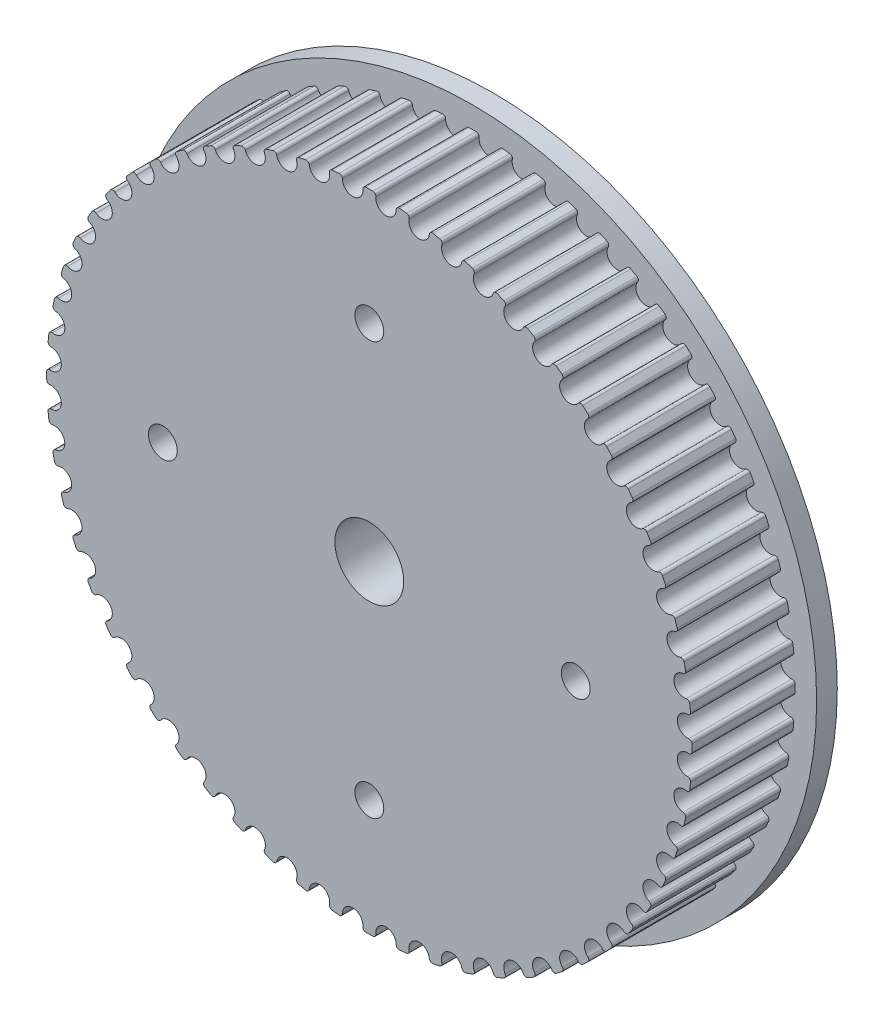
SolidWorks part; units mm, degrees
material "PE High Density"
ref_plane "Front Plane" through (0, 0, 0) normal (0, 0, 1) x (1, 0, 0)
ref_plane "Top Plane" through (0, 0, 0) normal (0, 1, 0) x (1, 0, 0)
ref_plane "Right Plane" through (0, 0, 0) normal (1, 0, 0) x (0, 0, -1)
sketch "Sketch2" plane through (0, 0, 0) normal (0, 0, 1) x (1, 0, 0)
  circle A0 centre (0, 0) radius 47.7465
  dimension "D1" = 95.493
extrude "PD" add sketch "Sketch2" along normal mid plane 15
sketch "Sketch3" plane through (0, 0, 7.5) normal (0, 0, 1) x (1, 0, 0)
  line L0 (0, 0) -> (0, 46.8765) construction
  line L1 (0, 0) -> (2.4235, 46.243) construction
  line L2 (0, 46.8765) -> (0.5143, 46.8765)
  line L3 (0, 46.8765) -> (0, 47.7465)
  line L4 (4.8999, 46.6197) -> (4.9909, 47.4849)
  line L5 (4.8999, 46.6197) -> (4.3884, 46.6734)
  line L6 (2.4235, 46.243) -> (2.4989, 47.681) construction
  arc A0 (0.5143, 46.8765) -> (0.9419, 46.4009) centre (0.5143, 46.4465) cw
  arc A1 (0.9419, 46.4009) -> (3.9135, 46.2452) centre (2.4235, 46.243) ccw
  circle A2 centre (0, 0) radius 47.7465 construction
  arc A3 (0, 47.7465) -> (4.9909, 47.4849) centre (0, 0) cw
  arc A4 (4.3884, 46.6734) -> (3.9135, 46.2452) centre (4.3435, 46.2458) ccw
  point P8 (2.3455, 44.7551)
  dimension "D1" = 0.43
  dimension "D2" = 1.49
  dimension "D3" = 0.87
  dimension "D4" = 3
  dimension "D5" = 2.93
extrude "Teeth" cut sketch "Sketch3" against normal up to surface (15 mm away) up to face at (47.7465, 0, -7.5)
pattern_circular "CirPattern1" count 60 over 360 about axis through (0, 0, 7.5) along (0, 0, 1) of "Teeth"
sketch "Sketch7" [suppressed] plane through (0, 0, -7.5) normal (0, 0, -1) x (-1, 0, 0)
  circle A0 centre (0, 6) radius 1.25
  circle A2 centre (6, 0) radius 1.25
  circle A3 centre (0, -6) radius 1.25
  circle A4 centre (-6, 0) radius 1.25
  point P12 (0, 0)
  dimension "D1" = 6
  dimension "D2" = 4
extrude "Cut-Extrude3" [suppressed] cut sketch "Sketch7" against normal blind 21
sketch "Sketch8" [suppressed] plane through (0, 0, -7.5) normal (0, 0, -1) x (-1, 0, 0)
  circle A0 centre (0, 0) radius 2.5
extrude "Cut-Extrude4" [suppressed] cut sketch "Sketch8" against normal blind 25
sketch "Sketch10" plane through (0, 0, -7.5) normal (0, 0, -1) x (-1, 0, 0)
  circle A0 centre (0, 0) radius 50
  dimension "D1" = 100
extrude "Boss-Extrude1" add sketch "Sketch10" along normal blind 3
sketch "Sketch12" [suppressed] plane through (0, 0, -7.5) normal (0, 0, -1) x (-1, 0, 0)
  circle A0 centre (0, 0) radius 13.5
  circle A1 centre (0, 6) radius 1.25 construction
  circle A2 centre (6, 0) radius 1.25 construction
  circle A3 centre (0, -6) radius 1.25 construction
  circle A4 centre (0, 0) radius 2.5 construction
  circle A5 centre (-6, 0) radius 1.25 construction
  circle A6 centre (0, 6) radius 1.25
  circle A7 centre (6, 0) radius 1.25
  circle A8 centre (0, -6) radius 1.25
  circle A9 centre (0, 0) radius 2.5
  circle A10 centre (-6, 0) radius 1.25
  dimension "D1" = 27
extrude "Boss-Extrude2" [suppressed] add sketch "Sketch12" along normal blind 3
sketch "Sketch13" [suppressed] plane through (0, 0, 7.5) normal (0, 0, 1) x (1, 0, 0)
  line L16 (0.3165, 11.8624) -> (-0.3165, 11.8624)
  line L17 (-4.2471, 11.0805) -> (-4.832, 10.8383)
  line L18 (-8.1642, 8.6118) -> (-8.6118, 8.1642)
  line L19 (-10.8383, 4.832) -> (-11.0805, 4.2471)
  line L20 (-11.8624, 0.3165) -> (-11.8624, -0.3165)
  line L21 (-11.0805, -4.2471) -> (-10.8383, -4.832)
  line L22 (-8.6118, -8.1642) -> (-8.1642, -8.6118)
  line L23 (-4.832, -10.8383) -> (-4.2471, -11.0805)
  line L24 (-0.3165, -11.8624) -> (0.3165, -11.8624)
  line L25 (4.2471, -11.0805) -> (4.832, -10.8383)
  line L26 (8.1642, -8.6118) -> (8.6118, -8.1642)
  line L27 (10.8383, -4.832) -> (11.0805, -4.2471)
  line L28 (11.8624, -0.3165) -> (11.8624, 0.3165)
  line L29 (11.0805, 4.2471) -> (10.8383, 4.832)
  line L30 (8.6118, 8.1642) -> (8.1642, 8.6118)
  line L31 (4.832, 10.8383) -> (4.2471, 11.0805)
  line L32 (0.3165, 11.8624) -> (-0.3165, 11.8624)
  line L33 (-4.2471, 11.0805) -> (-4.832, 10.8383)
  line L34 (-8.1642, 8.6118) -> (-8.6118, 8.1642)
  line L35 (-10.8383, 4.832) -> (-11.0805, 4.2471)
  line L36 (-11.8624, 0.3165) -> (-11.8624, -0.3165)
  line L37 (-11.0805, -4.2471) -> (-10.8383, -4.832)
  line L38 (-8.6118, -8.1642) -> (-8.1642, -8.6118)
  line L39 (-4.832, -10.8383) -> (-4.2471, -11.0805)
  line L40 (-0.3165, -11.8624) -> (0.3165, -11.8624)
  line L41 (4.2471, -11.0805) -> (4.832, -10.8383)
  line L42 (8.1642, -8.6118) -> (8.6118, -8.1642)
  line L43 (10.8383, -4.832) -> (11.0805, -4.2471)
  line L44 (11.8624, -0.3165) -> (11.8624, 0.3165)
  line L45 (11.0805, 4.2471) -> (10.8383, 4.832)
  line L46 (8.6118, 8.1642) -> (8.1642, 8.6118)
  line L47 (4.832, 10.8383) -> (4.2471, 11.0805)
  arc A48 (-0.3165, 11.8624) -> (-0.739, 11.3524) centre (-0.3165, 11.4324) ccw
  arc A49 (-3.6616, 10.7711) -> (-0.739, 11.3524) centre (-2.203, 11.0754) ccw
  arc A50 (-3.6616, 10.7711) -> (-4.2471, 11.0805) centre (-4.0826, 10.6833) ccw
  arc A51 (-4.832, 10.8383) -> (-5.0272, 10.2055) centre (-4.6674, 10.441) ccw
  arc A52 (-7.5048, 8.55) -> (-5.0272, 10.2055) centre (-6.2737, 9.3893) ccw
  arc A53 (-7.5048, 8.55) -> (-8.1642, 8.6118) centre (-7.8601, 8.3077) ccw
  arc A54 (-8.6118, 8.1642) -> (-8.55, 7.5048) centre (-8.3077, 7.8601) ccw
  arc A55 (-10.2055, 5.0272) -> (-8.55, 7.5048) centre (-9.3893, 6.2737) ccw
  arc A56 (-10.2055, 5.0272) -> (-10.8383, 4.832) centre (-10.441, 4.6674) ccw
  arc A57 (-11.0805, 4.2471) -> (-10.7711, 3.6616) centre (-10.6833, 4.0826) ccw
  arc A58 (-11.3524, 0.739) -> (-10.7711, 3.6616) centre (-11.0754, 2.203) ccw
  arc A59 (-11.3524, 0.739) -> (-11.8624, 0.3165) centre (-11.4324, 0.3165) ccw
  arc A60 (-11.8624, -0.3165) -> (-11.3524, -0.739) centre (-11.4324, -0.3165) ccw
  arc A61 (-10.7711, -3.6616) -> (-11.3524, -0.739) centre (-11.0754, -2.203) ccw
  arc A62 (-10.7711, -3.6616) -> (-11.0805, -4.2471) centre (-10.6833, -4.0826) ccw
  arc A63 (-10.8383, -4.832) -> (-10.2055, -5.0272) centre (-10.441, -4.6674) ccw
  arc A64 (-8.55, -7.5048) -> (-10.2055, -5.0272) centre (-9.3893, -6.2737) ccw
  arc A65 (-8.55, -7.5048) -> (-8.6118, -8.1642) centre (-8.3077, -7.8601) ccw
  arc A66 (-8.1642, -8.6118) -> (-7.5048, -8.55) centre (-7.8601, -8.3077) ccw
  arc A67 (-5.0272, -10.2055) -> (-7.5048, -8.55) centre (-6.2737, -9.3893) ccw
  arc A68 (-5.0272, -10.2055) -> (-4.832, -10.8383) centre (-4.6674, -10.441) ccw
  arc A69 (-4.2471, -11.0805) -> (-3.6616, -10.7711) centre (-4.0826, -10.6833) ccw
  arc A70 (-0.739, -11.3524) -> (-3.6616, -10.7711) centre (-2.203, -11.0754) ccw
  arc A71 (-0.739, -11.3524) -> (-0.3165, -11.8624) centre (-0.3165, -11.4324) ccw
  arc A72 (0.3165, -11.8624) -> (0.739, -11.3524) centre (0.3165, -11.4324) ccw
  arc A73 (3.6616, -10.7711) -> (0.739, -11.3524) centre (2.203, -11.0754) ccw
  arc A74 (3.6616, -10.7711) -> (4.2471, -11.0805) centre (4.0826, -10.6833) ccw
  arc A75 (4.832, -10.8383) -> (5.0272, -10.2055) centre (4.6674, -10.441) ccw
  arc A76 (7.5048, -8.55) -> (5.0272, -10.2055) centre (6.2737, -9.3893) ccw
  arc A77 (7.5048, -8.55) -> (8.1642, -8.6118) centre (7.8601, -8.3077) ccw
  arc A78 (8.6118, -8.1642) -> (8.55, -7.5048) centre (8.3077, -7.8601) ccw
  arc A79 (10.2055, -5.0272) -> (8.55, -7.5048) centre (9.3893, -6.2737) ccw
  arc A80 (10.2055, -5.0272) -> (10.8383, -4.832) centre (10.441, -4.6674) ccw
  arc A81 (11.0805, -4.2471) -> (10.7711, -3.6616) centre (10.6833, -4.0826) ccw
  arc A82 (11.3524, -0.739) -> (10.7711, -3.6616) centre (11.0754, -2.203) ccw
  arc A83 (11.3524, -0.739) -> (11.8624, -0.3165) centre (11.4324, -0.3165) ccw
  arc A84 (11.8624, 0.3165) -> (11.3524, 0.739) centre (11.4324, 0.3165) ccw
  arc A85 (10.7711, 3.6616) -> (11.3524, 0.739) centre (11.0754, 2.203) ccw
  arc A86 (10.7711, 3.6616) -> (11.0805, 4.2471) centre (10.6833, 4.0826) ccw
  arc A87 (10.8383, 4.832) -> (10.2055, 5.0272) centre (10.441, 4.6674) ccw
  arc A88 (8.55, 7.5048) -> (10.2055, 5.0272) centre (9.3893, 6.2737) ccw
  arc A89 (8.55, 7.5048) -> (8.6118, 8.1642) centre (8.3077, 7.8601) ccw
  arc A90 (8.1642, 8.6118) -> (7.5048, 8.55) centre (7.8601, 8.3077) ccw
  arc A91 (5.0272, 10.2055) -> (7.5048, 8.55) centre (6.2737, 9.3893) ccw
  arc A92 (5.0272, 10.2055) -> (4.832, 10.8383) centre (4.6674, 10.441) ccw
  arc A93 (4.2471, 11.0805) -> (3.6616, 10.7711) centre (4.0826, 10.6833) ccw
  arc A94 (0.739, 11.3524) -> (3.6616, 10.7711) centre (2.203, 11.0754) ccw
  arc A95 (0.739, 11.3524) -> (0.3165, 11.8624) centre (0.3165, 11.4324) ccw
  arc A96 (-0.3165, 11.8624) -> (-0.739, 11.3524) centre (-0.3165, 11.4324) ccw
  arc A97 (-3.6616, 10.7711) -> (-0.739, 11.3524) centre (-2.203, 11.0754) ccw
  arc A98 (-3.6616, 10.7711) -> (-4.2471, 11.0805) centre (-4.0826, 10.6833) ccw
  arc A99 (-4.832, 10.8383) -> (-5.0272, 10.2055) centre (-4.6674, 10.441) ccw
  arc A100 (-7.5048, 8.55) -> (-5.0272, 10.2055) centre (-6.2737, 9.3893) ccw
  arc A101 (-7.5048, 8.55) -> (-8.1642, 8.6118) centre (-7.8601, 8.3077) ccw
  arc A102 (-8.6118, 8.1642) -> (-8.55, 7.5048) centre (-8.3077, 7.8601) ccw
  arc A103 (-10.2055, 5.0272) -> (-8.55, 7.5048) centre (-9.3893, 6.2737) ccw
  arc A104 (-10.2055, 5.0272) -> (-10.8383, 4.832) centre (-10.441, 4.6674) ccw
  arc A105 (-11.0805, 4.2471) -> (-10.7711, 3.6616) centre (-10.6833, 4.0826) ccw
  arc A106 (-11.3524, 0.739) -> (-10.7711, 3.6616) centre (-11.0754, 2.203) ccw
  arc A107 (-11.3524, 0.739) -> (-11.8624, 0.3165) centre (-11.4324, 0.3165) ccw
  arc A108 (-11.8624, -0.3165) -> (-11.3524, -0.739) centre (-11.4324, -0.3165) ccw
  arc A109 (-10.7711, -3.6616) -> (-11.3524, -0.739) centre (-11.0754, -2.203) ccw
  arc A110 (-10.7711, -3.6616) -> (-11.0805, -4.2471) centre (-10.6833, -4.0826) ccw
  arc A111 (-10.8383, -4.832) -> (-10.2055, -5.0272) centre (-10.441, -4.6674) ccw
  arc A112 (-8.55, -7.5048) -> (-10.2055, -5.0272) centre (-9.3893, -6.2737) ccw
  arc A113 (-8.55, -7.5048) -> (-8.6118, -8.1642) centre (-8.3077, -7.8601) ccw
  arc A114 (-8.1642, -8.6118) -> (-7.5048, -8.55) centre (-7.8601, -8.3077) ccw
  arc A115 (-5.0272, -10.2055) -> (-7.5048, -8.55) centre (-6.2737, -9.3893) ccw
  arc A116 (-5.0272, -10.2055) -> (-4.832, -10.8383) centre (-4.6674, -10.441) ccw
  arc A117 (-4.2471, -11.0805) -> (-3.6616, -10.7711) centre (-4.0826, -10.6833) ccw
  arc A118 (-0.739, -11.3524) -> (-3.6616, -10.7711) centre (-2.203, -11.0754) ccw
  arc A119 (-0.739, -11.3524) -> (-0.3165, -11.8624) centre (-0.3165, -11.4324) ccw
  arc A120 (0.3165, -11.8624) -> (0.739, -11.3524) centre (0.3165, -11.4324) ccw
  arc A121 (3.6616, -10.7711) -> (0.739, -11.3524) centre (2.203, -11.0754) ccw
  arc A122 (3.6616, -10.7711) -> (4.2471, -11.0805) centre (4.0826, -10.6833) ccw
  arc A123 (4.832, -10.8383) -> (5.0272, -10.2055) centre (4.6674, -10.441) ccw
  arc A124 (7.5048, -8.55) -> (5.0272, -10.2055) centre (6.2737, -9.3893) ccw
  arc A125 (7.5048, -8.55) -> (8.1642, -8.6118) centre (7.8601, -8.3077) ccw
  arc A126 (8.6118, -8.1642) -> (8.55, -7.5048) centre (8.3077, -7.8601) ccw
  arc A127 (10.2055, -5.0272) -> (8.55, -7.5048) centre (9.3893, -6.2737) ccw
  arc A128 (10.2055, -5.0272) -> (10.8383, -4.832) centre (10.441, -4.6674) ccw
  arc A129 (11.0805, -4.2471) -> (10.7711, -3.6616) centre (10.6833, -4.0826) ccw
  arc A130 (11.3524, -0.739) -> (10.7711, -3.6616) centre (11.0754, -2.203) ccw
  arc A131 (11.3524, -0.739) -> (11.8624, -0.3165) centre (11.4324, -0.3165) ccw
  arc A132 (11.8624, 0.3165) -> (11.3524, 0.739) centre (11.4324, 0.3165) ccw
  arc A133 (10.7711, 3.6616) -> (11.3524, 0.739) centre (11.0754, 2.203) ccw
  arc A134 (10.7711, 3.6616) -> (11.0805, 4.2471) centre (10.6833, 4.0826) ccw
  arc A135 (10.8383, 4.832) -> (10.2055, 5.0272) centre (10.441, 4.6674) ccw
  arc A136 (8.55, 7.5048) -> (10.2055, 5.0272) centre (9.3893, 6.2737) ccw
  arc A137 (8.55, 7.5048) -> (8.6118, 8.1642) centre (8.3077, 7.8601) ccw
  arc A138 (8.1642, 8.6118) -> (7.5048, 8.55) centre (7.8601, 8.3077) ccw
  arc A139 (5.0272, 10.2055) -> (7.5048, 8.55) centre (6.2737, 9.3893) ccw
  arc A140 (5.0272, 10.2055) -> (4.832, 10.8383) centre (4.6674, 10.441) ccw
  arc A141 (4.2471, 11.0805) -> (3.6616, 10.7711) centre (4.0826, 10.6833) ccw
  arc A142 (0.739, 11.3524) -> (3.6616, 10.7711) centre (2.203, 11.0754) ccw
  arc A143 (0.739, 11.3524) -> (0.3165, 11.8624) centre (0.3165, 11.4324) ccw
  dimension "D1" = 0
sketch "Sketch14" plane through (0, 0, -10.5) normal (0, 0, -1) x (-1, 0, 0)
  line L0 (0.3165, 11.8624) -> (-0.3165, 11.8624)
  line L1 (-4.2471, 11.0805) -> (-4.832, 10.8383)
  line L2 (-8.1642, 8.6118) -> (-8.6118, 8.1642)
  line L3 (-10.8383, 4.832) -> (-11.0805, 4.2471)
  line L4 (-11.8624, 0.3165) -> (-11.8624, -0.3165)
  line L5 (-11.0805, -4.2471) -> (-10.8383, -4.832)
  line L6 (-8.6118, -8.1642) -> (-8.1642, -8.6118)
  line L7 (-4.832, -10.8383) -> (-4.2471, -11.0805)
  line L8 (-0.3165, -11.8624) -> (0.3165, -11.8624)
  line L9 (4.2471, -11.0805) -> (4.832, -10.8383)
  line L10 (8.1642, -8.6118) -> (8.6118, -8.1642)
  line L11 (10.8383, -4.832) -> (11.0805, -4.2471)
  line L12 (11.8624, -0.3165) -> (11.8624, 0.3165)
  line L13 (11.0805, 4.2471) -> (10.8383, 4.832)
  line L14 (8.6118, 8.1642) -> (8.1642, 8.6118)
  line L15 (4.832, 10.8383) -> (4.2471, 11.0805)
  line L16 (-4.5395, 10.9594) -> (4.5395, -10.9594) construction
  arc A0 (-0.3165, 11.8624) -> (-0.739, 11.3524) centre (-0.3165, 11.4324) ccw
  arc A1 (-3.6616, 10.7711) -> (-0.739, 11.3524) centre (-2.203, 11.0754) ccw
  arc A2 (-3.6616, 10.7711) -> (-4.2471, 11.0805) centre (-4.0826, 10.6833) ccw
  arc A3 (-4.832, 10.8383) -> (-5.0272, 10.2055) centre (-4.6674, 10.441) ccw
  arc A4 (-7.5048, 8.55) -> (-5.0272, 10.2055) centre (-6.2737, 9.3893) ccw
  arc A5 (-7.5048, 8.55) -> (-8.1642, 8.6118) centre (-7.8601, 8.3077) ccw
  arc A6 (-8.6118, 8.1642) -> (-8.55, 7.5048) centre (-8.3077, 7.8601) ccw
  arc A7 (-10.2055, 5.0272) -> (-8.55, 7.5048) centre (-9.3893, 6.2737) ccw
  arc A8 (-10.2055, 5.0272) -> (-10.8383, 4.832) centre (-10.441, 4.6674) ccw
  arc A9 (-11.0805, 4.2471) -> (-10.7711, 3.6616) centre (-10.6833, 4.0826) ccw
  arc A10 (-11.3524, 0.739) -> (-10.7711, 3.6616) centre (-11.0754, 2.203) ccw
  arc A11 (-11.3524, 0.739) -> (-11.8624, 0.3165) centre (-11.4324, 0.3165) ccw
  arc A12 (-11.8624, -0.3165) -> (-11.3524, -0.739) centre (-11.4324, -0.3165) ccw
  arc A13 (-10.7711, -3.6616) -> (-11.3524, -0.739) centre (-11.0754, -2.203) ccw
  arc A14 (-10.7711, -3.6616) -> (-11.0805, -4.2471) centre (-10.6833, -4.0826) ccw
  arc A15 (-10.8383, -4.832) -> (-10.2055, -5.0272) centre (-10.441, -4.6674) ccw
  arc A16 (-8.55, -7.5048) -> (-10.2055, -5.0272) centre (-9.3893, -6.2737) ccw
  arc A17 (-8.55, -7.5048) -> (-8.6118, -8.1642) centre (-8.3077, -7.8601) ccw
  arc A18 (-8.1642, -8.6118) -> (-7.5048, -8.55) centre (-7.8601, -8.3077) ccw
  arc A19 (-5.0272, -10.2055) -> (-7.5048, -8.55) centre (-6.2737, -9.3893) ccw
  arc A20 (-5.0272, -10.2055) -> (-4.832, -10.8383) centre (-4.6674, -10.441) ccw
  arc A21 (-4.2471, -11.0805) -> (-3.6616, -10.7711) centre (-4.0826, -10.6833) ccw
  arc A22 (-0.739, -11.3524) -> (-3.6616, -10.7711) centre (-2.203, -11.0754) ccw
  arc A23 (-0.739, -11.3524) -> (-0.3165, -11.8624) centre (-0.3165, -11.4324) ccw
  arc A24 (0.3165, -11.8624) -> (0.739, -11.3524) centre (0.3165, -11.4324) ccw
  arc A25 (3.6616, -10.7711) -> (0.739, -11.3524) centre (2.203, -11.0754) ccw
  arc A26 (3.6616, -10.7711) -> (4.2471, -11.0805) centre (4.0826, -10.6833) ccw
  arc A27 (4.832, -10.8383) -> (5.0272, -10.2055) centre (4.6674, -10.441) ccw
  arc A28 (7.5048, -8.55) -> (5.0272, -10.2055) centre (6.2737, -9.3893) ccw
  arc A29 (7.5048, -8.55) -> (8.1642, -8.6118) centre (7.8601, -8.3077) ccw
  arc A30 (8.6118, -8.1642) -> (8.55, -7.5048) centre (8.3077, -7.8601) ccw
  arc A31 (10.2055, -5.0272) -> (8.55, -7.5048) centre (9.3893, -6.2737) ccw
  arc A32 (10.2055, -5.0272) -> (10.8383, -4.832) centre (10.441, -4.6674) ccw
  arc A33 (11.0805, -4.2471) -> (10.7711, -3.6616) centre (10.6833, -4.0826) ccw
  arc A34 (11.3524, -0.739) -> (10.7711, -3.6616) centre (11.0754, -2.203) ccw
  arc A35 (11.3524, -0.739) -> (11.8624, -0.3165) centre (11.4324, -0.3165) ccw
  arc A36 (11.8624, 0.3165) -> (11.3524, 0.739) centre (11.4324, 0.3165) ccw
  arc A37 (10.7711, 3.6616) -> (11.3524, 0.739) centre (11.0754, 2.203) ccw
  arc A38 (10.7711, 3.6616) -> (11.0805, 4.2471) centre (10.6833, 4.0826) ccw
  arc A39 (10.8383, 4.832) -> (10.2055, 5.0272) centre (10.441, 4.6674) ccw
  arc A40 (8.55, 7.5048) -> (10.2055, 5.0272) centre (9.3893, 6.2737) ccw
  arc A41 (8.55, 7.5048) -> (8.6118, 8.1642) centre (8.3077, 7.8601) ccw
  arc A42 (8.1642, 8.6118) -> (7.5048, 8.55) centre (7.8601, 8.3077) ccw
  arc A43 (5.0272, 10.2055) -> (7.5048, 8.55) centre (6.2737, 9.3893) ccw
  arc A44 (5.0272, 10.2055) -> (4.832, 10.8383) centre (4.6674, 10.441) ccw
  arc A45 (4.2471, 11.0805) -> (3.6616, 10.7711) centre (4.0826, 10.6833) ccw
  arc A46 (0.739, 11.3524) -> (3.6616, 10.7711) centre (2.203, 11.0754) ccw
  arc A47 (0.739, 11.3524) -> (0.3165, 11.8624) centre (0.3165, 11.4324) ccw
  point P114 (0, 0)
extrude "Boss-Extrude3" add sketch "Sketch14" along normal blind 15
sketch "Sketch15" plane through (0, 0, -25.5) normal (0, 0, -1) x (-1, 0, 0)
  circle A0 centre (0, 0) radius 13.5
  dimension "D1" = 27
extrude "Boss-Extrude4" add sketch "Sketch15" along normal blind 3 contours A0
sketch "Sketch16" plane through (0, 0, -28.5) normal (0, 0, -1) x (-1, 0, 0)
  circle A0 centre (0, 0) radius 5
extrude "Cut-Extrude5" cut sketch "Sketch16" against normal through all both and the other way through all
sketch "Sketch17" plane through (0, 0, 7.5) normal (0, 0, 1) x (1, 0, 0)
  line L0 (0, 0) -> (0, 30) construction
  circle A0 centre (0, 30) radius 2.1
  circle A1 centre (30, 0) radius 2.1
  circle A2 centre (0, -30) radius 2.1
  circle A3 centre (-30, 0) radius 2.1
  point P13 (0, 0)
  dimension "D1" = 4.2
  dimension "D2" = 4
extrude "Cut-Extrude6" cut sketch "Sketch17" against normal through all both
sketch "Sketch18" plane through (0, 0, -10.5) normal (0, 0, -1) x (-1, 0, 0)
  circle A1 centre (30, 0) radius 2.1 construction
  circle A26 centre (30, 0) radius 2.1 construction
  circle A27 centre (0, 30) radius 2.1 construction
  circle A28 centre (-30, 0) radius 2.1 construction
  circle A29 centre (0, -30) radius 2.1 construction
  circle A30 centre (0, 30) radius 2.1 construction
  circle A31 centre (-30, 0) radius 2.1 construction
  circle A32 centre (0, -30) radius 2.1 construction
  circle A33 centre (30, 0) radius 3.85
  circle A34 centre (0, 30) radius 3.85
  circle A35 centre (-30, 0) radius 3.85
  circle A36 centre (0, -30) radius 3.85
  dimension "D1" = 1.75
extrude "Cut-Extrude7" cut sketch "Sketch18" against normal blind 6
sketch "Sketch19" plane through (0, 0, -10.5) normal (0, 0, -1) x (-1, 0, 0)
  line L0 (0, 0) -> (0, 30) construction
  circle A0 centre (0, 0) radius 5
  circle A1 centre (0, 30) radius 2.1
  circle A2 centre (30, 0) radius 2.1
  circle A3 centre (0, -30) radius 2.1
  circle A4 centre (-30, 0) radius 2.1
  point P14 (0, 0)
  dimension "D1" = 10
  dimension "D3" = 4.2
  dimension "D2" = 30
  dimension "D4" = 4
extrude "Cut-Extrude8" [suppressed] cut sketch "Sketch19" against normal through all
sketch "Sketch21" [suppressed] plane through (0, 0, -10.5) normal (0, 0, -1) x (-1, 0, 0)
  circle A0 centre (0, 30) radius 2.1 construction
  circle A1 centre (30, 0) radius 2.1 construction
  circle A5 centre (-30, 0) radius 2.1 construction
  circle A6 centre (0, -30) radius 2.1 construction
  circle A7 centre (-30, 0) radius 2.1 construction
  circle A8 centre (0, -30) radius 2.1 construction
  circle A9 centre (30, 0) radius 2.1 construction
  circle A10 centre (0, 30) radius 2.1 construction
  circle A11 centre (-30, 0) radius 3.85
  circle A12 centre (0, -30) radius 3.85
  circle A13 centre (30, 0) radius 3.85
  circle A14 centre (0, 30) radius 3.85
  dimension "D1" = 1.75
extrude "Cut-Extrude9" [suppressed] cut sketch "Sketch21" against normal blind 5
equation "\"D1@Sketch4\"= 16 + 2"
equation "\"D1\" = 16"
equation "\"D4@Sketch3\" = 180 / 16"
equation "\"D1@Sketch2\" = 16 * 5 / pi"
